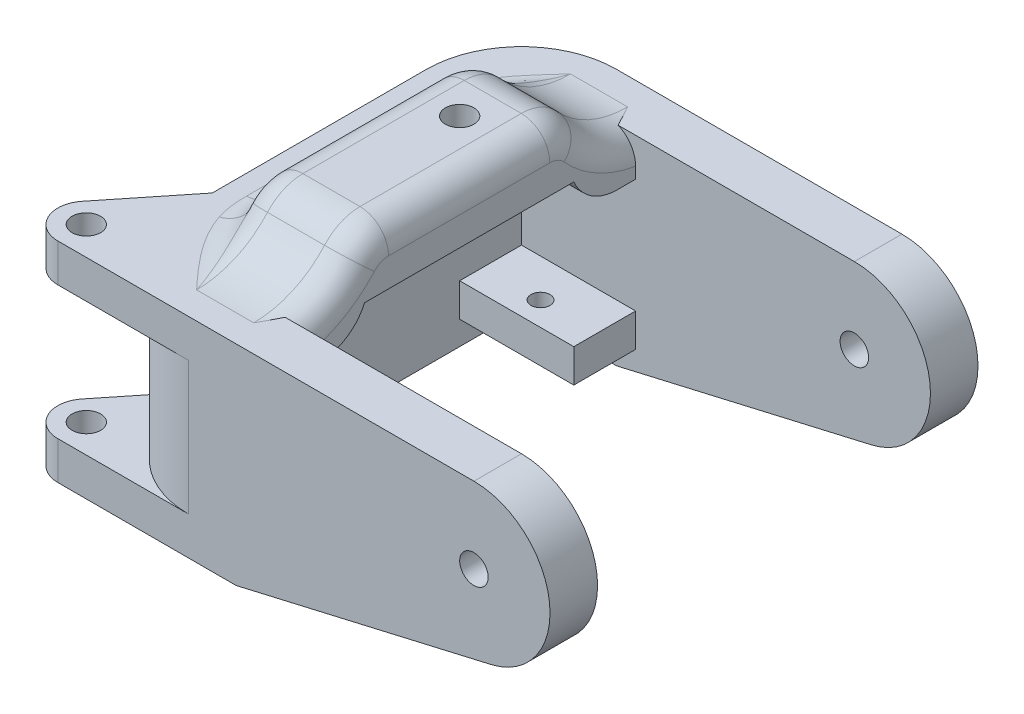
SolidWorks part; units mm, degrees
ref_plane "前视基准面" through (0, 0, 0) normal (0, 0, 1) x (1, 0, 0)
ref_plane "上视基准面" through (0, 0, 0) normal (0, 1, 0) x (1, 0, 0)
ref_plane "右视基准面" through (0, 0, 0) normal (1, 0, 0) x (0, 0, -1)
sketch "草图1" plane through (0, 0, 0) normal (0, 0, 1) x (1, 0, 0)
  line L0 (0.5609, -11) -> (27.3655, -4.7938)
  line L1 (0.5609, -11) -> (-14.4391, -11)
  line L3 (0.5609, 11) -> (-14.4391, 11)
  line L4 (-14.4391, -11) -> (-14.4391, 11)
  line L7 (0.5609, 11) -> (25.5609, 11)
  arc A1 (27.3655, -4.7938) -> (25.5609, 11) centre (25.5609, 3) ccw
  circle A2 centre (25.5609, 3) radius 1.5
  point P0 (0, 0)
  dimension "D4" = 8
  dimension "D5" = 3
  dimension "D1" = 22
  dimension "D2" = 15
  dimension "D3" = 25
extrude "凸台-拉伸1" add sketch "草图1" along normal blind 45
sketch "草图2" plane through (0, 11, 0) normal (0, 1, 0) x (1, 0, 0)
  line L0 (25.5609, 0) -> (-14.4391, 0) construction
  line L1 (-9.4391, -5) -> (42.9728, -5)
  line L2 (-9.4391, -5) -> (-9.4391, -40)
  line L3 (-9.4391, -40) -> (42.9728, -40)
  line L4 (42.9728, -5) -> (42.9728, -40)
  line L7 (-14.4391, -45) -> (-14.4391, 0) construction
  dimension "D1" = 35
  dimension "D2" = 52.4118
  dimension "D3" = 5
  dimension "D4" = 5
extrude "切除-拉伸1" cut sketch "草图2" against normal through all
sketch "草图4" plane through (0, -11, 0) normal (0, -1, 0) x (1, 0, 0)
  line L1 (-9.4391, 40) -> (2.5609, 40)
  line L2 (-9.4391, 40) -> (-9.4391, 33.5)
  line L3 (-9.4391, 33.5) -> (2.5609, 33.5)
  line L4 (2.5609, 40) -> (2.5609, 33.5)
  line L5 (-9.4391, 5) -> (2.5609, 5)
  line L6 (-9.4391, 5) -> (-9.4391, 11.5)
  line L7 (-9.4391, 11.5) -> (2.5609, 11.5)
  line L8 (2.5609, 5) -> (2.5609, 11.5)
  dimension "D1" = 6.5
  dimension "D2" = 12
  dimension "D3" = 6.5
  dimension "D4" = 12
extrude "凸台-拉伸2" add sketch "草图4" against normal blind 12
sketch "草图6" plane through (2.5609, 0, 0) normal (1, 0, 0) x (0, 0, -1)
  line L1 (-33.5, -11) -> (-40, -11)
  line L2 (-33.5, -11) -> (-33.5, -8.5)
  line L3 (-33.5, -8.5) -> (-40, -8.5)
  line L4 (-40, -11) -> (-40, -8.5)
  line L5 (-40, 1) -> (-40, -10.5369) construction
  line L7 (-11.5, -11) -> (-5, -11)
  line L8 (-11.5, -11) -> (-11.5, -8.5)
  line L9 (-11.5, -8.5) -> (-5, -8.5)
  line L10 (-5, -11) -> (-5, -8.5)
  line L11 (-5, -4.7938) -> (-5, -10.5369) construction
  dimension "D1" = 2.5
  dimension "D2" = 6.5
  dimension "D3" = 2.5
  dimension "D4" = 6.5
extrude "切除-拉伸2" cut sketch "草图6" against normal blind 12
sketch "草图7" plane through (0, -8.5, 0) normal (0, -1, 0) x (1, 0, 0)
  line L0 (-1009.4391, 22.5) -> (48990.5609, 22.5) construction
  line L1 (-9.4391, 5) -> (-9.4391, 40) construction
  line L2 (-9.4391, 33.5) -> (2.5609, 33.5) construction
  line L3 (-9.4391, 33.5) -> (-9.4391, 40) construction
  circle A0 centre (-3.4391, 36) radius 1
  circle A1 centre (-3.4391, 9) radius 1
  point P5 (-9.4391, 22.5)
  point P9 (-3.4391, 33.5)
  dimension "D1" = 2.5
  dimension "D2" = 6
extrude "切除-拉伸3" cut sketch "草图7" against normal blind 12
sketch "草图9" plane through (0, -11, 0) normal (0, -1, 0) x (1, 0, 0)
  line L0 (-14.4391, 45) -> (-18.1941, 45)
  line L1 (-20.536, 40.125) -> (-14.4391, 32.51)
  line L3 (-14.4391, 45) -> (-14.4391, 0) construction
  line L4 (-14.4391, 45) -> (-14.4391, 32.51)
  arc A0 (-18.1941, 45) -> (-20.536, 40.125) centre (-18.1941, 42) ccw
  circle A1 centre (-18.1941, 42) radius 1.5
  dimension "D1" = 3
  dimension "D3" = 6
extrude "凸台-拉伸3" add sketch "草图9" against normal blind 22
sketch "草图10" plane through (-14.4391, 0, 0) normal (-1, 0, 0) x (0, 0, 1)
  line L0 (40.125, 0) -> (-49959.875, 0) construction
  line L1 (40.125, 11) -> (40.125, -11) construction
  line L3 (50.1195, -7) -> (30.1305, -7)
  line L4 (50.1195, -7) -> (50.1195, 7)
  line L5 (50.1195, 7) -> (30.1305, 7)
  line L6 (30.1305, -7) -> (30.1305, 7)
  line L7 (50.1195, -7) -> (30.1305, 7) construction
  line L8 (50.1195, 7) -> (30.1305, -7) construction
  point P4 (40.125, 0)
  point P5 (40.125, 0)
  dimension "D1" = 14
  dimension "D2" = 19.9889
extrude "切除-拉伸4" cut sketch "草图10" along normal through all
sketch "草图12" plane through (0, 1, 0) normal (0, 1, 0) x (1, 0, 0)
  line L1 (-9.4391, -5) -> (2.5609, -5)
  line L2 (-9.4391, -5) -> (-9.4391, -11.5)
  line L3 (-9.4391, -11.5) -> (2.5609, -11.5)
  line L4 (2.5609, -5) -> (2.5609, -11.5)
  line L5 (-9.4391, -33.5) -> (2.5609, -33.5)
  line L6 (-9.4391, -33.5) -> (-9.4391, -40)
  line L7 (-9.4391, -40) -> (2.5609, -40)
  line L8 (2.5609, -33.5) -> (2.5609, -40)
  dimension "D1" = 6.5
  dimension "D2" = 12
  dimension "D3" = 6.5
  dimension "D4" = 12
extrude "切除-拉伸5" cut sketch "草图12" against normal blind 6
sketch "草图13" plane through (-9.4391, 0, 0) normal (1, 0, 0) x (0, 0, -1)
  line L1 (-40, 11) -> (-5, 11)
  line L2 (-40, 11) -> (-40, 7)
  line L3 (-40, 7) -> (-5, 7)
  line L4 (-5, 11) -> (-5, 7)
  line L5 (-5, -5) -> (-5, 11) construction
  dimension "D1" = 4
  dimension "D2" = 35
extrude "凸台-拉伸4" add sketch "草图13" along normal blind 12
sketch "草图14" plane through (0, 11, 0) normal (0, 1, 0) x (1, 0, 0)
  line L1 (-9.4391, -33.5) -> (2.5609, -33.5)
  line L2 (-9.4391, -33.5) -> (-9.4391, -11.5)
  line L3 (-9.4391, -11.5) -> (2.5609, -11.5)
  line L4 (2.5609, -33.5) -> (2.5609, -11.5)
  dimension "D1" = 22
  dimension "D2" = 12
extrude "凸台-拉伸5" add sketch "草图14" along normal blind 5
sketch "草图15" plane through (0, 7, 0) normal (0, -1, 0) x (1, 0, 0)
  line L1 (2.5609, 11.5) -> (-9.4391, 11.5)
  line L2 (2.5609, 11.5) -> (2.5609, 33.5)
  line L3 (2.5609, 33.5) -> (-9.4391, 33.5)
  line L4 (-9.4391, 11.5) -> (-9.4391, 33.5)
  dimension "D1" = 22
  dimension "D2" = 12
extrude "切除-拉伸6" cut sketch "草图15" against normal blind 3
fillet "圆角1" radius 10 2 edges at (-3.4391, 11, 11.5) (-3.4391, 11, 33.5)
fillet "圆角2" radius 5 2 edges at (-3.4391, 16, 11.5) (-3.4391, 16, 33.5)
fillet "圆角4" radius 5 2 edges at (-3.4391, 7, 11.5) (-3.4391, 7, 33.5)
sketch "草图16" plane through (0, 10, 0) normal (0, -1, 0) x (1, 0, 0)
  circle A0 centre (-3.4391, 17.5) radius 1.5
  dimension "D1" = 3
extrude "切除-拉伸7" cut sketch "草图16" against normal blind 10
fillet "圆角7" radius 3 5 edges at (-9.4391, 11.8713, 6.9222) (-9.4391, 15.5644, 11.9788) (-9.4391, 16, 22.5) (-9.4391, 15.5644, 33.0212) (-9.4391, 11.8713, 38.0778)
fillet "圆角8" radius 3 3 edges at (-8.9752, 11, 8.308) (-8.9752, 11, 36.692) (-9.4391, 11, 22.5)
sketch "草图17" plane through (0, 10, 0) normal (0, -1, 0) x (1, 0, 0)
  line L1 (-3.4391, 20.0981) -> (-5.6891, 18.799)
  line L2 (-5.6891, 18.799) -> (-5.6891, 16.201)
  line L3 (-5.6891, 16.201) -> (-3.4391, 14.9019)
  line L4 (-3.4391, 14.9019) -> (-1.1891, 16.201)
  line L5 (-1.1891, 16.201) -> (-1.1891, 18.799)
  line L6 (-1.1891, 18.799) -> (-3.4391, 20.0981)
  circle A0 centre (-3.4391, 17.5) radius 2.25 construction
  point P1 (-1.1891, 17.5)
  dimension "D1" = 4.5
extrude "切除-拉伸8" cut sketch "草图17" against normal blind 2
fillet "圆角9" radius 3 5 edges at (2.5609, 15.5644, 33.0212) (2.5609, 15.5644, 11.9788) (2.5609, 11.8713, 6.9222) (2.5609, 11.8713, 38.0778) (2.5609, 16, 22.5)
fillet "圆角10" radius 10 2 edges at (-14.4391, 0, 0) (-14.4391, 0, 45)
sketch "草图19" plane through (0, 0, 0) normal (0, 0, -1) x (-1, 0, 0)
  circle A0 centre (-25.5609, 3) radius 3
  dimension "D1" = 6
